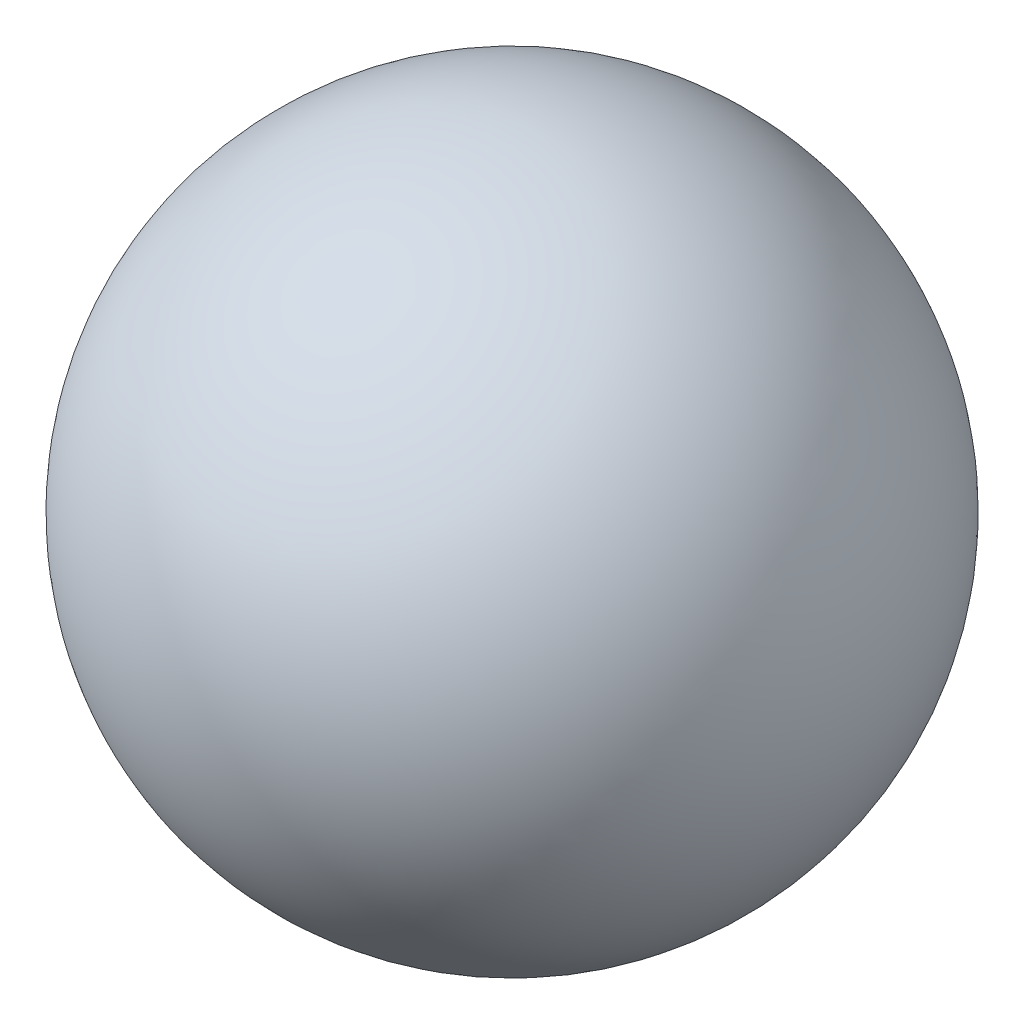
SolidWorks part; units mm, degrees
material "Plain Carbon Steel"
ref_plane "Front Plane" through (0, 0, 0) normal (0, 0, 1) x (1, 0, 0)
ref_plane "Top Plane" through (0, 0, 0) normal (0, 1, 0) x (1, 0, 0)
ref_plane "Right Plane" through (0, 0, 0) normal (1, 0, 0) x (0, 0, -1)
sketch "Sketch1" plane through (0, 0, 0) normal (1, 0, 0) x (0, 0, -1)
  line L0 (0, 0) -> (-14.2498, 0) construction
  line L1 (0, 0) -> (26.2357, 0) construction
  line L2 (-2.38, 0) -> (2.38, 0)
  arc A0 (2.38, 0) -> (-2.38, 0) centre (0, 0) ccw
  dimension "D1" = 4.76
revolve "Revolve1" add sketch "Sketch1" angle 360 about L0
ref_axis "Axis1" through (0, 0, 2.618) along (0, 0, -1)
